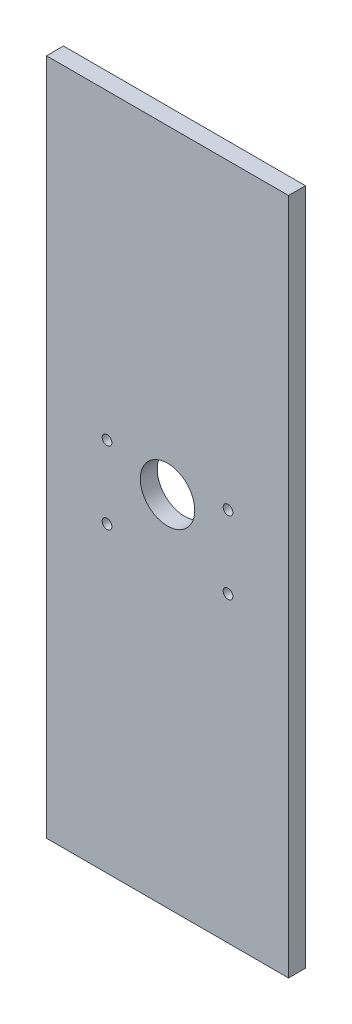
SolidWorks part; units mm, degrees
material "Balsa"
ref_plane "Front Plane" through (0, 0, 0) normal (0, 0, 1) x (1, 0, 0)
ref_plane "Top Plane" through (0, 0, 0) normal (0, 1, 0) x (1, 0, 0)
ref_plane "Right Plane" through (0, 0, 0) normal (1, 0, 0) x (0, 0, -1)
sketch "Sketch1" plane through (0, 0, 0) normal (0, 0, 1) x (1, 0, 0)
  line L1 (-63.5, 177.8) -> (63.5, 177.8)
  line L2 (-63.5, 177.8) -> (-63.5, -177.8)
  line L3 (-63.5, -177.8) -> (63.5, -177.8)
  line L4 (63.5, 177.8) -> (63.5, -177.8)
  line L5 (-63.5, 177.8) -> (63.5, -177.8) construction
  line L6 (-63.5, -177.8) -> (63.5, 177.8) construction
  line L7 (-63.5, -177.8) -> (63.5, -177.8) construction
  point P0 (0, 0)
  dimension "D1" = 355.6
  dimension "D2" = 127
extrude "Boss-Extrude1" add sketch "Sketch1" along normal mid plane 8.89
sketch "Sketch2" plane through (0, 0, 4.445) normal (0, 0, 1) x (1, 0, 0)
  line L1 (31.75, -19.05) -> (-31.75, -19.05) construction
  line L2 (31.75, -19.05) -> (31.75, 19.05) construction
  line L3 (31.75, 19.05) -> (-31.75, 19.05) construction
  line L4 (-31.75, -19.05) -> (-31.75, 19.05) construction
  line L5 (31.75, -19.05) -> (-31.75, 19.05) construction
  line L6 (31.75, 19.05) -> (-31.75, -19.05) construction
  circle A5 centre (0, 10.125) radius 14.2875
  circle A9 centre (31.75, 19.05) radius 2.54
  circle A10 centre (31.75, -19.05) radius 2.54
  circle A11 centre (-31.75, -19.05) radius 2.54
  circle A12 centre (-31.75, 19.05) radius 2.54
  point P0 (0, 0)
  point P7 (0, 0)
  point P9 (-95.2403, -6.1668)
  point P10 (0, 0)
  point P11 (0, 0)
  point P12 (0, 0)
  point P16 (0, 8.3995)
  dimension "D1" = 28.575
  dimension "D3" = 63.5
  dimension "D5" = 5.08
  dimension "D2" = 10.125
  dimension "D4" = 38.1
extrude "Cut-Extrude1" cut sketch "Sketch2" against normal through all contours A11 | A12 A5 | A5 A12 | A9 | A10 region at (0, 10.125, 4.445) region at (31.75, 19.05, 4.445) region at (31.75, -19.05, 4.445) region at (-31.75, -19.05, 4.445) region at (-31.75, 19.05, 4.445)
ref_axis "Axis1" through (0, 10.125, -4.445) along (0, 0, 1)
